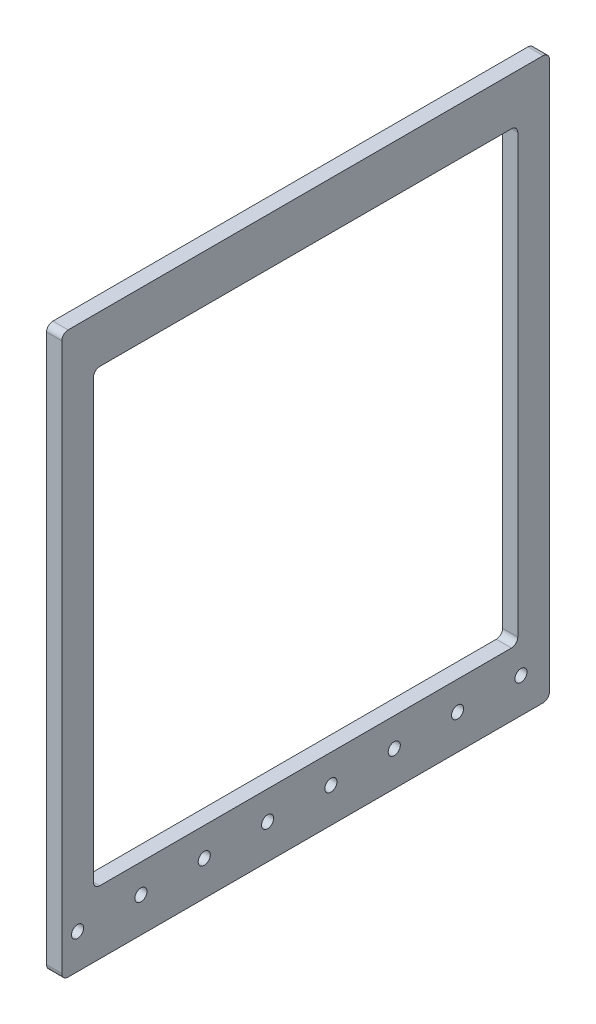
SolidWorks part; units mm, degrees
ref_plane "Front Plane" through (0, 0, 0) normal (0, 0, 1) x (1, 0, 0)
ref_plane "Top Plane" through (0, 0, 0) normal (0, 1, 0) x (1, 0, 0)
ref_plane "Right Plane" through (0, 0, 0) normal (1, 0, 0) x (0, 0, -1)
sketch "Sketch1" plane through (0, 0, 0) normal (1, 0, 0) x (0, 0, -1)
  line L1 (0, 0) -> (170.18, 0)
  line L2 (0, 0) -> (0, -180.34)
  line L3 (0, -180.34) -> (170.18, -180.34)
  line L4 (170.18, 0) -> (170.18, -180.34)
  line L5 (-12.7, 19.05) -> (182.88, 19.05)
  line L6 (-12.7, 19.05) -> (-12.7, -205.74)
  line L7 (-12.7, -205.74) -> (182.88, -205.74)
  line L8 (182.88, 19.05) -> (182.88, -205.74)
  circle A1 centre (-6.35, -191.77) radius 2.425
  circle A2 centre (19.05, -191.77) radius 2.425
  circle A3 centre (44.45, -191.77) radius 2.425
  circle A4 centre (69.85, -191.77) radius 2.425
  circle A5 centre (95.25, -191.77) radius 2.425
  circle A6 centre (120.65, -191.77) radius 2.425
  circle A7 centre (146.05, -191.77) radius 2.425
  circle A8 centre (171.45, -191.77) radius 2.425
  dimension "D7" = 8
  dimension "D8" = 4.85
  dimension "D9" = 6.35
  dimension "D1" = 180.34
  dimension "D2" = 170.18
  dimension "D3" = 19.05
  dimension "D4" = 12.7
  dimension "D5" = 12.7
  dimension "D6" = 25.4
extrude "Boss-Extrude1" add sketch "Sketch1" along normal blind 6.096
fillet "Fillet1" radius 2.54 8 edges at (3.048, 19.05, -182.88) (3.048, 19.05, 12.7) (3.048, -205.74, -182.88) (3.048, -205.74, 12.7) (3.048, -180.34, 0) (3.048, -180.34, -170.18) (3.048, 0, -170.18) (3.048, 0, 0)
